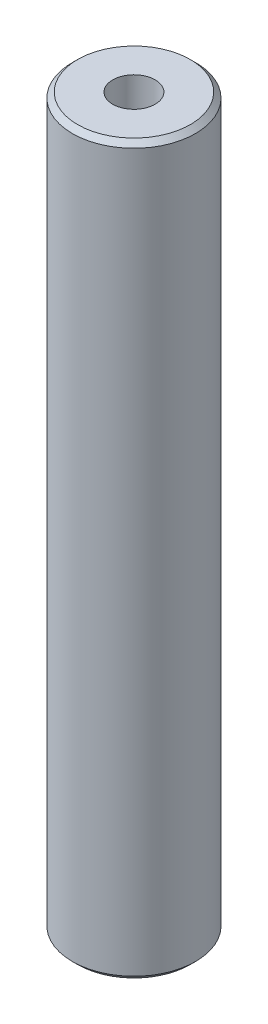
SolidWorks part; units mm, degrees
ref_plane "Front Plane" through (0, 0, 0) normal (0, 0, 1) x (1, 0, 0)
ref_plane "Top Plane" through (0, 0, 0) normal (0, 1, 0) x (1, 0, 0)
ref_plane "Right Plane" through (0, 0, 0) normal (1, 0, 0) x (0, 0, -1)
sketch "Sketch1" plane through (0, 0, 0) normal (0, 1, 0) x (1, 0, 0)
  circle A0 centre (0, 0) radius 50
  dimension "SHAFT_OD" = 100
extrude "Boss-Extrude1" add sketch "Sketch1" along normal blind 590.6869
sketch "Sketch2" plane through (0, 0, 0) normal (0, 1, 0) x (1, 0, 0)
  circle A0 centre (0, 0) radius 17.2145
  dimension "BORE_D" = 34.429
extrude "Cut-Extrude1" cut sketch "Sketch2" along normal through all
chamfer "Chamfer1" distance 4.207 angle 45 2 edges at (0, 590.6869, 50) (0, 0, 50)
